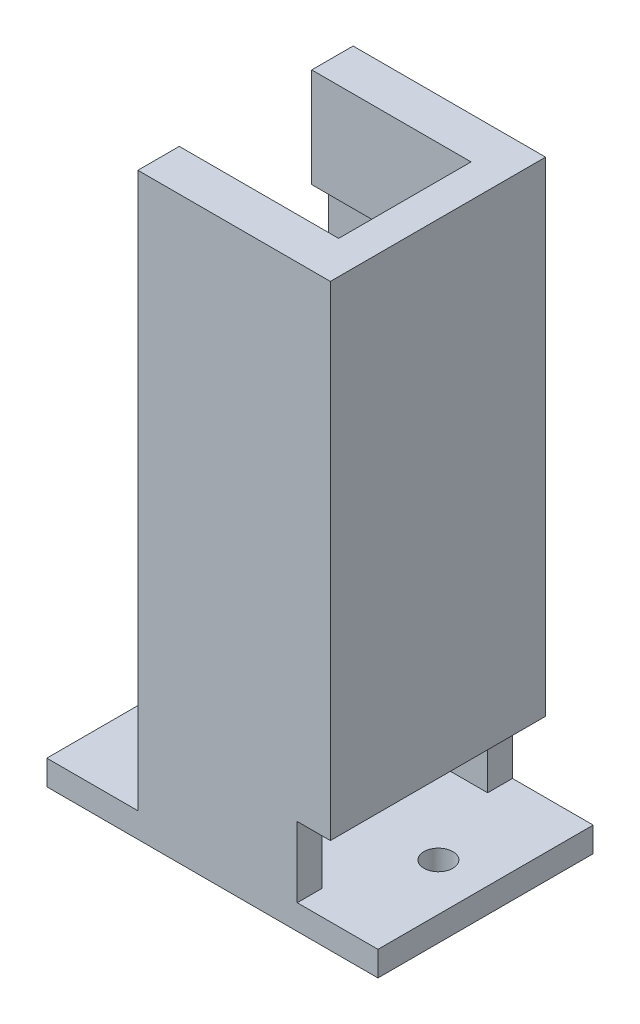
SolidWorks part; units mm, degrees
ref_plane "Front Plane" through (0, 0, 0) normal (0, 0, 1) x (1, 0, 0)
ref_plane "Top Plane" through (0, 0, 0) normal (0, 1, 0) x (1, 0, 0)
ref_plane "Right Plane" through (0, 0, 0) normal (1, 0, 0) x (0, 0, -1)
sketch "Sketch1" plane through (0, 0, 0) normal (0, 1, 0) x (1, 0, 0)
  line L1 (-20, 13) -> (20, 13)
  line L2 (-20, 13) -> (-20, -13)
  line L3 (-20, -13) -> (20, -13)
  line L4 (20, 13) -> (20, -13)
  dimension "D1" = 40
  dimension "D2" = 26
  dimension "D3" = 13
  dimension "D4" = 20
extrude "Boss-Extrude1" add sketch "Sketch1" along normal blind 3 contours L1 L4 L3 L2
sketch "Sketch2" plane through (0, 3, 0) normal (0, 1, 0) x (1, 0, 0)
  line L0 (20, 0) -> (14.3, 0) construction
  line L1 (20, 13) -> (20, -13) construction
  line L2 (0, 13) -> (0, -13) construction
  line L3 (-20, 13) -> (20, 13) construction
  line L4 (-20, -13) -> (20, -13) construction
  line L5 (-20, 0) -> (-14.3, 0) construction
  circle A0 centre (14.3, 0) radius 1.75
  circle A1 centre (-14.3, 0) radius 1.75
extrude "Cut-Extrude1" cut sketch "Sketch2" against normal blind 3
sketch "Sketch3" plane through (0, 3, 0) normal (0, 1, 0) x (1, 0, 0)
  line L0 (-20, 13) -> (20, 13) construction
  line L1 (0, 0) -> (50000, 0) construction
  line L2 (0, 0) -> (0, 50000) construction
  line L3 (-9, -10) -> (10.25, -10)
  line L4 (-9, 13) -> (10.25, 13)
  line L5 (-9, 13) -> (-9, 10)
  line L6 (-9, 10) -> (10.25, 10)
  line L7 (10.25, 13) -> (10.25, 10)
  line L8 (10.25, -13) -> (10.25, -10)
  line L9 (-9, -13) -> (10.25, -13)
  line L10 (-9, -13) -> (-9, -10)
  line L11 (0, 0) -> (10.5, 0) construction
  point P0 (-9, 13)
  point P9 (9, 13)
  point P20 (0, 0)
  dimension "D1" = 11
  dimension "D2" = 3
  dimension "D3" = 19.25
extrude "Boss-Extrude2" add sketch "Sketch3" along normal blind 55
sketch "Sketch5" plane through (0, 58, 0) normal (0, 1, 0) x (1, 0, 0)
  line L0 (-9, 13) -> (-9, -13) construction
  line L1 (-9, -8) -> (-9, 8) construction
  line L2 (-9, 0) -> (49991, 0) construction
  line L3 (-9, 13) -> (10.25, 13)
  line L4 (-9, 13) -> (-9, 8)
  line L5 (-9, 8) -> (10.25, 8)
  line L6 (10.25, 13) -> (10.25, 8)
  line L11 (-9, -8) -> (10.25, -8)
  line L12 (10.25, -13) -> (10.25, -8)
  line L13 (-9, -13) -> (10.25, -13)
  line L14 (-9, -13) -> (-9, -8)
  point P7 (-9, 0)
  dimension "D1" = 26
  dimension "D2" = 19.25
extrude "Boss-Extrude4" add sketch "Sketch5" along normal blind 12
sketch "Sketch6" plane through (0, 3, 0) normal (0, 1, 0) x (1, 0, 0)
  circle A0 centre (0, 0) radius 2.5
extrude "Cut-Extrude2" cut sketch "Sketch6" against normal blind 15
sketch "Sketch7" plane through (10.25, 0, 0) normal (1, 0, 0) x (0, 0, -1)
  line L0 (-13, 3) -> (-13, 11.5) construction
  line L1 (-13, 70) -> (-13, 3) construction
  line L3 (-13, 11.5) -> (13, 11.5)
  line L4 (-13, 11.5) -> (-13, 70)
  line L5 (-13, 70) -> (13, 70)
  line L6 (13, 11.5) -> (13, 70)
extrude "Boss-Extrude5" add sketch "Sketch7" along normal blind 4
